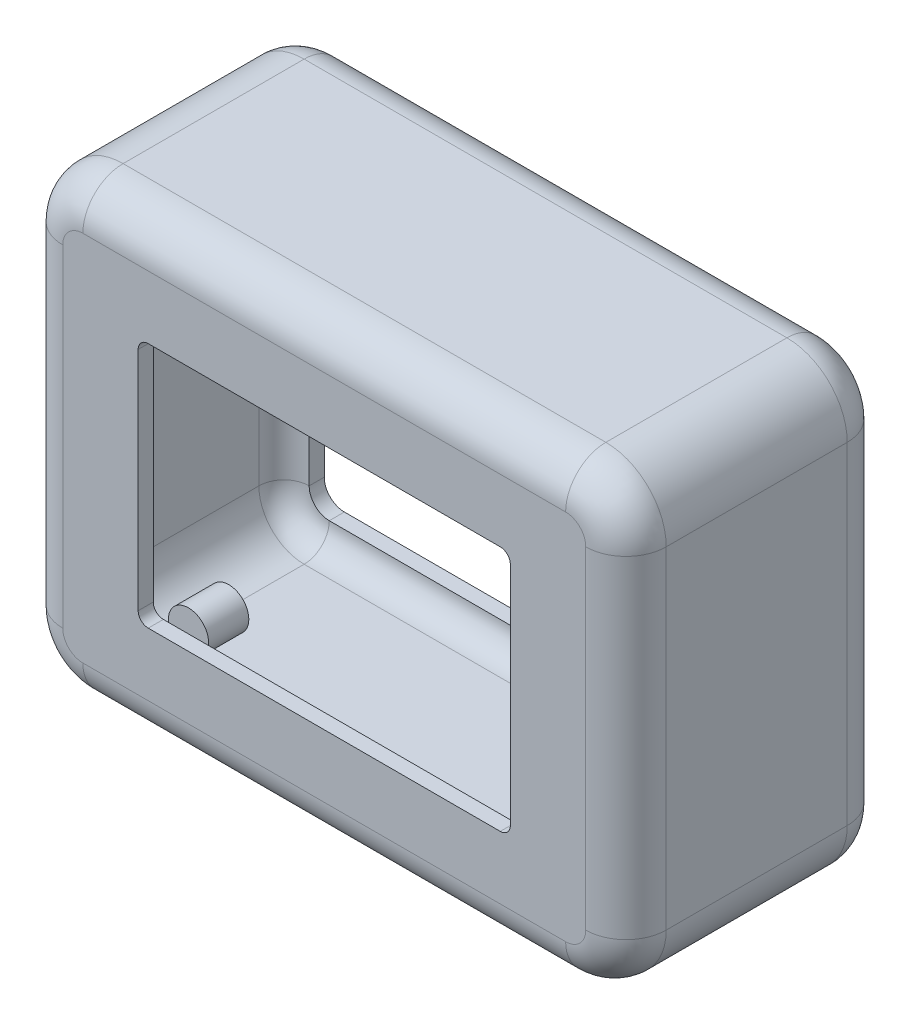
SolidWorks part; units mm, degrees
ref_plane "Front Plane" through (0, 0, 0) normal (0, 0, 1) x (1, 0, 0)
ref_plane "Top Plane" through (0, 0, 0) normal (0, 1, 0) x (1, 0, 0)
ref_plane "Right Plane" through (0, 0, 0) normal (1, 0, 0) x (0, 0, -1)
sketch "Sketch1" plane through (0, 0, 0) normal (0, 0, 1) x (1, 0, 0)
  line L1 (-48, 45) -> (48, 45)
  line L2 (-60, 33) -> (-60, -33)
  line L3 (-48, -45) -> (48, -45)
  line L4 (60, 33) -> (60, -33)
  line L5 (-60, 45) -> (60, -45) construction
  line L6 (-60, -45) -> (60, 45) construction
  arc A0 (48, 45) -> (60, 33) centre (48, 33) cw
  arc A1 (48, -45) -> (60, -33) centre (48, -33) ccw
  arc A2 (-60, -33) -> (-48, -45) centre (-48, -33) ccw
  arc A3 (-48, 45) -> (-60, 33) centre (-48, 33) ccw
  point P0 (0, 0)
  dimension "D3" = 12
  dimension "D1" = 120
  dimension "D2" = 90
extrude "Boss-Extrude1" add sketch "Sketch1" along normal mid plane 52
fillet "Fillet1" radius 8 16 edges at (60, 0, -26) (0, -45, -26) (-60, 0, -26) (0, 45, -26) (0, 45, 26) (60, 0, 26) (0, -45, 26) (-60, 0, 26) (-56.4853, 41.4853, -26) (-56.4853, -41.4853, -26) (56.4853, -41.4853, -26) (56.4853, 41.4853, -26) (56.4853, 41.4853, 26) (56.4853, -41.4853, 26) (-56.4853, -41.4853, 26) (-56.4853, 41.4853, 26)
shell "Shell1" thickness 3 removed face at (0, 0, -26)
sketch "Sketch2" plane through (0, 0, 26) normal (0, 0, 1) x (1, 0, 0)
  line L1 (-35, -24.5) -> (35, -24.5)
  line L2 (-37, -22.5) -> (-37, 22.5)
  line L3 (-35, 24.5) -> (35, 24.5)
  line L4 (37, -22.5) -> (37, 22.5)
  line L5 (-37, -24.5) -> (37, 24.5) construction
  line L6 (-37, 24.5) -> (37, -24.5) construction
  arc A0 (35, 24.5) -> (37, 22.5) centre (35, 22.5) cw
  arc A1 (35, -24.5) -> (37, -22.5) centre (35, -22.5) ccw
  arc A2 (-35, -24.5) -> (-37, -22.5) centre (-35, -22.5) cw
  arc A3 (-37, 22.5) -> (-35, 24.5) centre (-35, 22.5) cw
  point P0 (0, 0)
  dimension "D3" = 2
  dimension "D1" = 49
  dimension "D2" = 74
extrude "Cut-Extrude1" cut sketch "Sketch2" against normal up to next
sketch "Sketch3" plane through (0, 0, 0) normal (0, 0, 1) x (1, 0, 0)
  circle A0 centre (45, 39) radius 4
  circle A1 centre (-45, 39) radius 4
  circle A2 centre (-45, -39) radius 4
  circle A3 centre (45, -39) radius 4
  dimension "D1" = 8
  dimension "D2" = 8
  dimension "D3" = 8
  dimension "D4" = 8
  dimension "D5" = 45
  dimension "D6" = 39
  dimension "D7" = 45
  dimension "D8" = 39
  dimension "D9" = 39
  dimension "D10" = 45
  dimension "D11" = 45
  dimension "D12" = 39
extrude "Boss-Extrude2" add sketch "Sketch3" along normal blind 8
